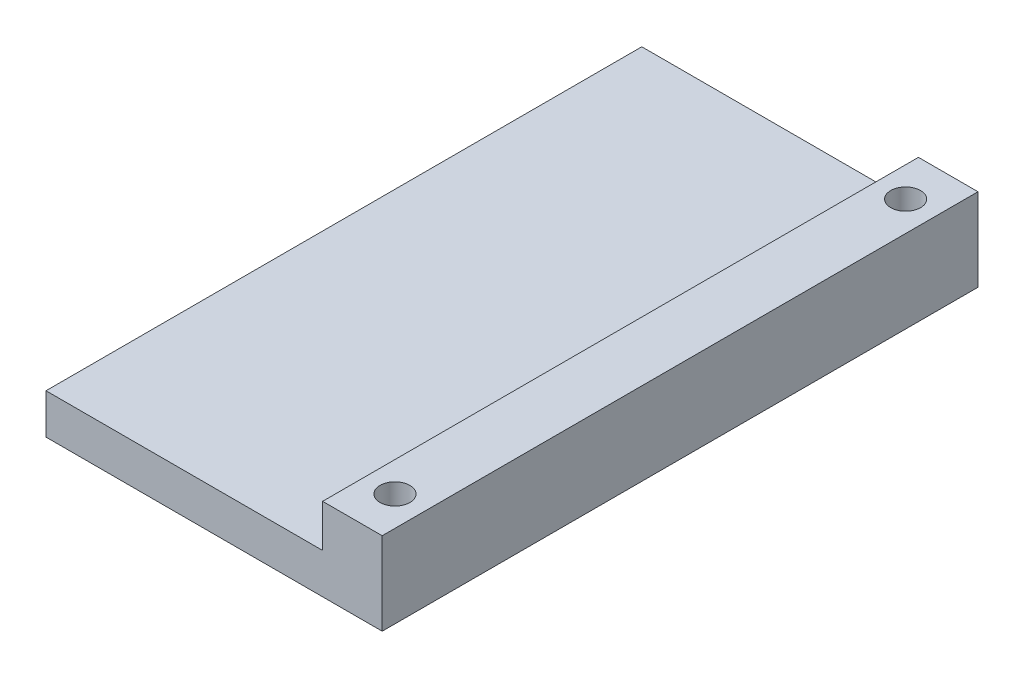
SolidWorks part; units mm, degrees
ref_plane "Front Plane" through (0, 0, 0) normal (0, 0, 1) x (1, 0, 0)
ref_plane "Top Plane" through (0, 0, 0) normal (0, 1, 0) x (1, 0, 0)
ref_plane "Right Plane" through (0, 0, 0) normal (1, 0, 0) x (0, 0, -1)
sketch "Sketch1" plane through (0, 0, 0) normal (0, 1, 0) x (1, 0, 0)
  line L1 (0, 0) -> (41.275, 0)
  line L2 (0, 0) -> (0, 88.9)
  line L3 (0, 88.9) -> (41.275, 88.9)
  line L4 (41.275, 0) -> (41.275, 88.9)
  line L5 (41.275, 88.9) -> (50.165, 88.9)
  line L6 (41.275, 88.9) -> (41.275, 0)
  line L7 (41.275, 0) -> (50.165, 0)
  line L8 (50.165, 88.9) -> (50.165, 0)
  dimension "D1" = 41.275
  dimension "D2" = 88.9
  dimension "D3" = 8.89
extrude "Boss-Extrude1" add sketch "Sketch1" along normal blind 5.9944 contours L1 L4 L3 L2 region at (20.6375, 0, -44.45)
extrude "Boss-Extrude2" add sketch "Sketch1<5>" along normal blind 12.3444 contours L8 L5 L4 L7 region at (45.72, 0, -44.45)
sketch "Sketch1<5>" plane through (0, 0, 0) normal (0, 1, 0) x (1, 0, 0) same geometry as "Sketch1"
sketch "Sketch3" plane through (0, 12.3444, 0) normal (0, 1, 0) x (1, 0, 0)
  line L0 (45.72, 82.55) -> (45.72, 6.35) construction
  line L1 (50.165, 88.9) -> (50.165, 0) construction
  line L2 (41.275, 88.9) -> (50.165, 88.9) construction
  line L3 (0, 0) -> (0, 88.9) construction
  circle A0 centre (45.72, 82.55) radius 2.2225
  circle A1 centre (45.72, 6.35) radius 2.2225
  point P4 (45.72, 44.45)
  point P6 (50.165, 44.45)
  point P7 (45.72, 88.9)
  dimension "D1" = 4.445
  dimension "D2" = 4.445
  dimension "D3" = 76.2
  dimension "D4" = 45.72
extrude "Cut-Extrude1" cut sketch "Sketch3" against normal through all both contours A1 | A0
